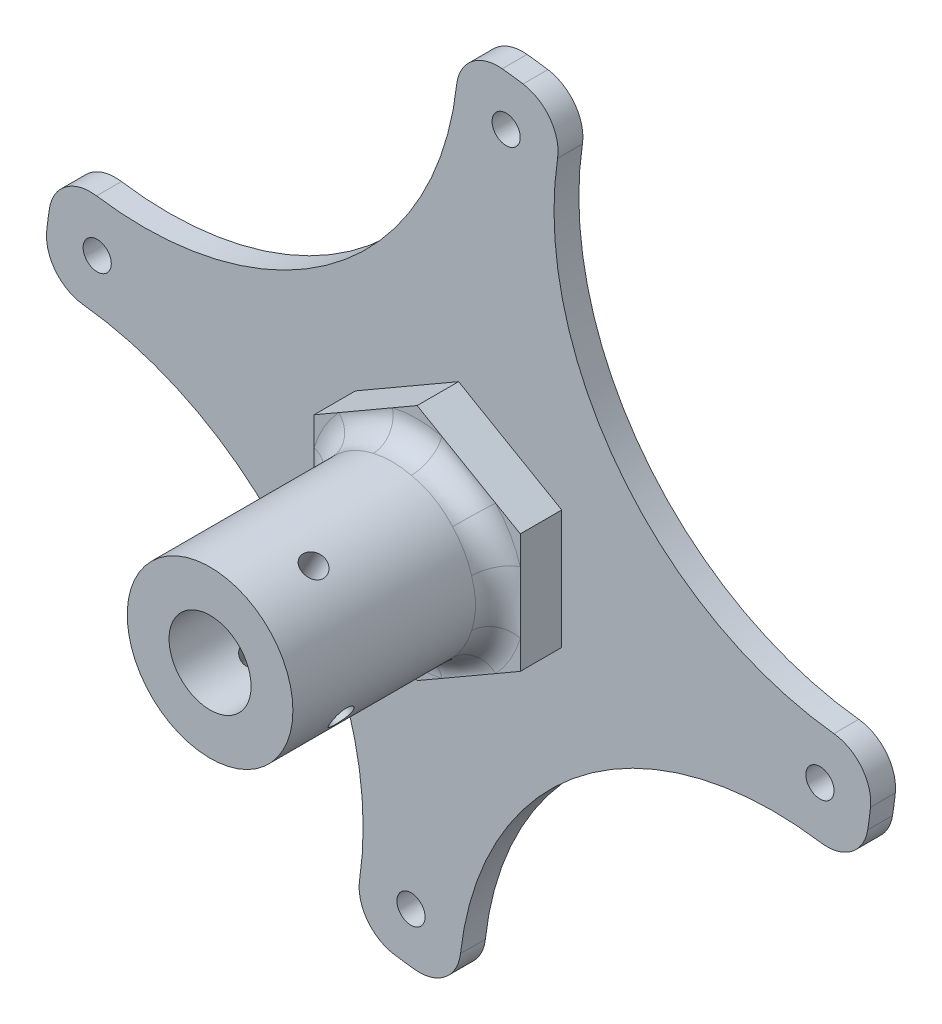
SolidWorks part; units mm, degrees
ref_plane "Front Plane" through (0, 0, 0) normal (0, 0, 1) x (1, 0, 0)
ref_plane "Top Plane" through (0, 0, 0) normal (0, 1, 0) x (1, 0, 0)
ref_plane "Right Plane" through (0, 0, 0) normal (1, 0, 0) x (0, 0, -1)
sketch "Sketch1" plane through (0, 0, 0) normal (0, 0, 1) x (1, 0, 0)
  circle A0 centre (0, 0) radius 50
  dimension "D1" = 100
extrude "Boss-Extrude1" add sketch "Sketch1" along normal blind 3
sketch "Sketch2" plane through (0, 0, 3) normal (0, 0, 1) x (1, 0, 0)
  line L1 (12.45, -7.188) -> (12.45, 7.188)
  line L2 (12.45, 7.188) -> (0, 14.376)
  line L3 (0, 14.376) -> (-12.45, 7.188)
  line L4 (-12.45, 7.188) -> (-12.45, -7.188)
  line L5 (-12.45, -7.188) -> (0, -14.376)
  line L6 (0, -14.376) -> (12.45, -7.188)
  circle A0 centre (0, 0) radius 12.45 construction
  dimension "D1" = 24.9
extrude "Boss-Extrude2" add sketch "Sketch2" along normal blind 5
sketch "Sketch3" plane through (0, 0, 8) normal (0, 0, 1) x (1, 0, 0)
  circle A0 centre (0, 0) radius 10
  dimension "D1" = 20
extrude "Boss-Extrude3" add sketch "Sketch3" along normal blind 25
fillet "Fillet1" radius 3 1 edges at (10, 0, 8)
sketch "Sketch4" plane through (0, 0, 33) normal (0, 0, 1) x (1, 0, 0)
  circle A0 centre (0, 0) radius 4.95
  dimension "D1" = 9.9
extrude "Cut-Extrude1" cut sketch "Sketch4" against normal through all
hole_wizard "Ø1.0mm Dowel Hole1" positions "3DSketch1" profile "Sketch5" hole size "Ø1.0" standard "ANSI Metric"
sketch3d "3DSketch1"
  point P0 (-8.696, 4.9375, 25.8574)
  point P2 (4.8442, 8.7483, 25.3286)
sketch "Sketch5" plane through (-8.696, 4.9375, 25.8574) normal (0, 0, 1) x (-0.4938, -0.8696, 0)
  line L0 (0, 0) -> (0, 34)
  line L1 (0, 34) -> (1.4, 33.1588)
  line L2 (1.4, 33.1588) -> (1.4, 0)
  line L5 (1.4, 0) -> (0, 0)
  line L10 (0, 34) -> (-1.4, 33.1588) construction
  line L11 (0, -6.35) -> (0, 107.95) construction
  dimension "Hole Dia." = 2.8
  dimension "Hole Depth" = 34
  dimension "Drill Angle" = 118
sketch "Sketch6" plane through (0, 0, 3) normal (0, 0, 1) x (1, 0, 0)
  line L0 (-50, 0) -> (0, 0)
  line L1 (0, 0) -> (-48.2963, 12.941)
  arc A0 (0, 50) -> (-48.2963, 12.941) centre (-37.997, 49.5186) cw
  circle A1 centre (0, 0) radius 50 construction
  arc A2 (-48.2963, 12.941) -> (0, 50) centre (0, 0) ccw
  arc A3 (50, 0) -> (12.941, 48.2963) centre (49.5186, 37.997) cw
  arc A4 (0, -50) -> (48.2963, -12.941) centre (37.997, -49.5186) cw
  arc A5 (-50, 0) -> (-12.941, -48.2963) centre (-49.5186, -37.997) cw
  point P21 (0, 0)
  circle M9 centre (0, 0) radius 50
  dimension "D1" = 38
  dimension "D3" = 4
  dimension "15" = 15
extrude "Cut-Extrude2" cut sketch "Sketch6" against normal blind 25 contours A0 L1 M9 | A3 A2 | A4 A2 | A5 L0 M9 region at (-29.8164, -22.879, 3) region at (-22.8789, 29.8165, 3) region at (22.879, -29.8164, 3) region at (29.8164, 22.879, 3)
fillet "Fillet2" radius 5 8 edges at (-48.2963, 12.941, 1.5) (-50, 0, 1.5) (-12.941, -48.2963, 1.5) (0, -50, 1.5) (48.2963, -12.941, 1.5) (50, 0, 1.5) (0, 50, 1.5) (12.941, 48.2963, 1.5)
sketch "Sketch7" plane through (0, 0, 0) normal (0, 0, -1) x (-1, 0, 0)
  line L0 (-6.5263, 49.5722) -> (0, 0) construction
  arc A0 (-5.2642, 49.7221) -> (-7.7842, 49.3903) centre (0, 0) ccw construction
  point P0 (-5.7432, 43.6236)
  point P10 (43.6236, 5.7432)
  point P11 (5.7432, -43.6236)
  point P12 (-43.6236, -5.7432)
  point P13 (0, 0)
  dimension "D1" = 6
  dimension "D2" = 4
hole_wizard "Ø1.0mm Dowel Hole2" positions "3DSketch2" profile "Sketch8" hole size "Ø1.0" standard "ANSI Metric"
sketch3d "3DSketch2"
  point P0 (5.7432, 43.6236, 0)
  point P3 (-43.6236, 5.7432, 0)
  point P6 (-5.7432, -43.6236, 0)
  point P9 (43.6236, -5.7432, 0)
sketch "Sketch8" plane through (5.7432, 43.6236, 0) normal (1, 0, 0) x (0, 1, 0)
  line L0 (0, 0) -> (0, 34)
  line L1 (0, 34) -> (1.7, 32.9785)
  line L2 (1.7, 32.9785) -> (1.7, 0)
  line L5 (1.7, 0) -> (0, 0)
  line L10 (0, 34) -> (-1.7, 32.9785) construction
  line L11 (0, -6.35) -> (0, 107.95) construction
  dimension "Hole Dia." = 3.4
  dimension "Hole Depth" = 34
  dimension "Drill Angle" = 118
